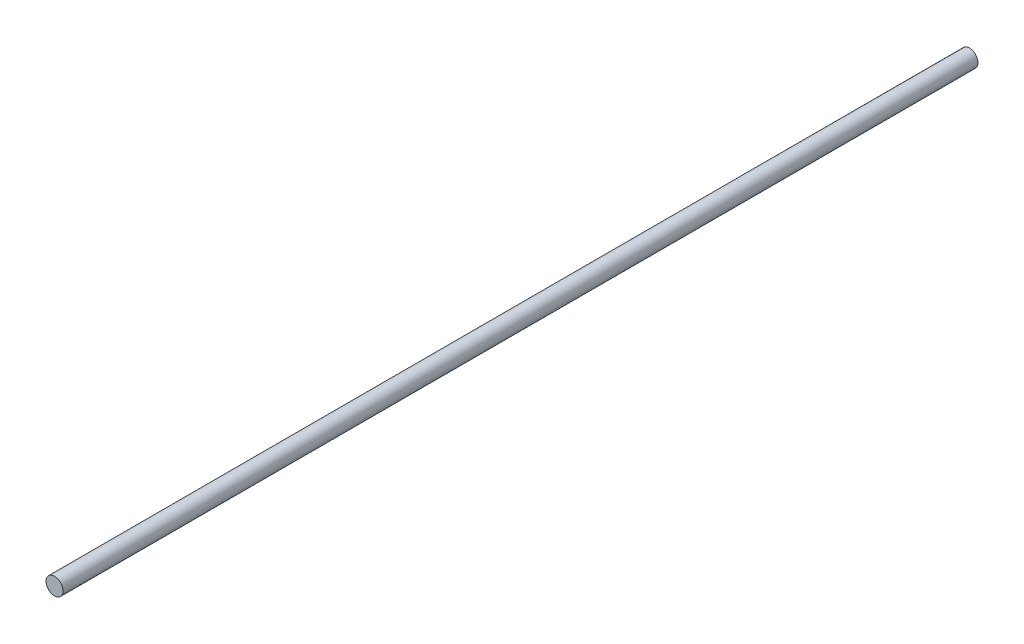
SolidWorks part; units mm, degrees
material "AISI 316 Stainless Steel Sheet (SS)"
ref_plane "Front (1)" through (0, 0, 0) normal (0, 0, 1) x (1, 0, 0)
ref_plane "Top (2)" through (0, 0, 0) normal (0, 1, 0) x (1, 0, 0)
ref_plane "Right (3)" through (0, 0, 0) normal (1, 0, 0) x (0, 0, -1)
ref_axis "X Axis" through (13.5064, 0, 0) along (-1, 0, 0)
ref_axis "Y Axis" through (0, 12.3593, 0) along (0, -1, 0)
ref_axis "Z Axis" through (0, 0, 14.1119) along (0, 0, -1)
sketch "Sketch2" plane through (0, 0, 0) normal (1, 0, 0) x (0, 0, -1)
  line L1 (0, 0) -> (430, 0)
  line L2 (0, 0) -> (0, 4)
  line L3 (0, 4) -> (430, 4)
  line L4 (430, 0) -> (430, 4)
  dimension "D1" = 430
  dimension "D2" = 4
revolve "Revolve1" add sketch "Sketch2" angle 360 about L1
cosmetic thread "Cosmetic Thread2" parameters "D2"=6.891
